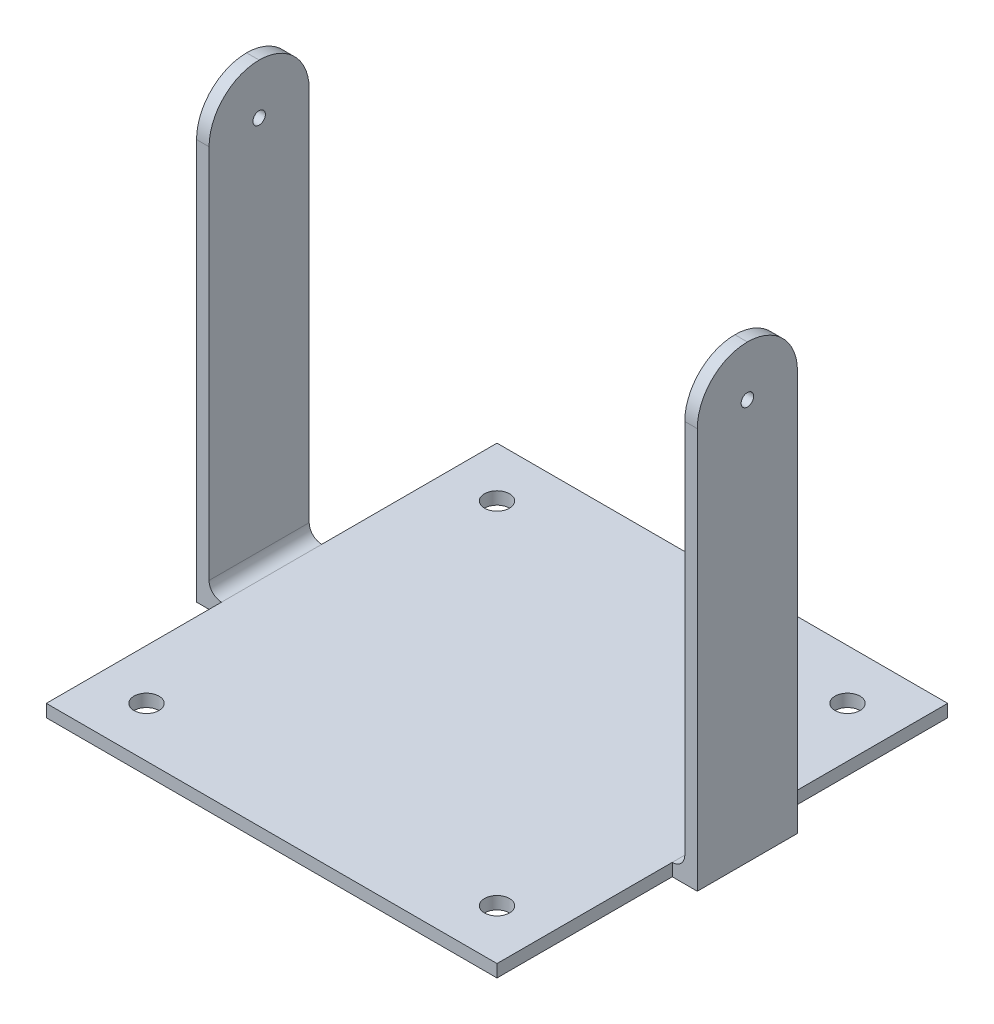
SolidWorks part; units mm, degrees
material "6061 Alloy"
ref_plane "Front Plane" through (0, 0, 0) normal (0, 0, 1) x (1, 0, 0)
ref_plane "Top Plane" through (0, 0, 0) normal (0, 1, 0) x (1, 0, 0)
ref_plane "Right Plane" through (0, 0, 0) normal (1, 0, 0) x (0, 0, -1)
sketch "Sketch1" plane through (0, 0, 0) normal (0, 1, 0) x (1, 0, 0)
  line L1 (0, 0) -> (228.6, 0)
  line L2 (0, 0) -> (0, 457.2)
  line L3 (0, 457.2) -> (228.6, 457.2)
  line L4 (228.6, 0) -> (228.6, 457.2)
  dimension "D1" = 228.6
  dimension "D2" = 457.2
extrude "Boss-Extrude1" add sketch "Sketch1" along normal blind 12.7
sketch "Sketch2" plane through (0, 12.7, 0) normal (0, 1, 0) x (1, 0, 0)
  line L0 (114.3, 457.2) -> (114.3, 0) construction
  line L1 (228.6, 457.2) -> (0, 457.2) construction
  line L2 (0, 0) -> (228.6, 0) construction
  line L3 (0, 228.6) -> (228.6, 228.6) construction
  line L4 (0, 457.2) -> (0, 0) construction
  line L5 (228.6, 0) -> (228.6, 457.2) construction
  line L7 (228.6, 279.4) -> (241.3, 279.4)
  line L8 (228.6, 279.4) -> (228.6, 177.8)
  line L9 (228.6, 177.8) -> (241.3, 177.8)
  line L10 (241.3, 279.4) -> (241.3, 177.8)
  dimension "D1" = 12.7
  dimension "D2" = 101.6
  dimension "D3" = 50.8
extrude "Boss-Extrude2" add sketch "Sketch2" against normal blind 12.7
sketch "Sketch3" plane through (241.3, 0, 0) normal (1, 0, 0) x (0, 0, -1)
  line L1 (177.8, 0) -> (279.4, 0)
  line L2 (177.8, 0) -> (177.8, 457.2)
  line L3 (177.8, 457.2) -> (279.4, 457.2)
  line L4 (279.4, 0) -> (279.4, 457.2)
  dimension "D1" = 101.6
  dimension "D2" = 457.2
extrude "Boss-Extrude3" add sketch "Sketch3" along normal blind 12.7
fillet "Fillet1" radius 12.7 1 edges
mirror "Mirror1" about plane through (0, 12.7, 0) normal (1, 0, 0) of "Boss-Extrude1", "Boss-Extrude2", "Boss-Extrude3", "Fillet1"
sketch "Sketch4" plane through (-254, 0, 0) normal (-1, 0, 0) x (0, 0, 1)
  line L0 (-279.4, 457.2) -> (-177.8, 457.2) construction
  line L1 (-279.4, 0) -> (-279.4, 457.2) construction
  circle A0 centre (-228.6, 406.4) radius 6.35
  dimension "D1" = 12.7
  dimension "D2" = 50.8
  dimension "D3" = 50.8
extrude "Cut-Extrude1" cut sketch "Sketch4" against normal through all
fillet "Fillet2" radius 50.8 1 edges at (-247.65, 457.2, -177.8)
fillet "Fillet3" radius 50.8 1 edges at (-247.65, 457.2, -279.4)
fillet "Fillet4" radius 50.8 1 edges at (247.65, 457.2, -177.8)
fillet "Fillet5" radius 50.8 1 edges at (247.65, 457.2, -279.4)
sketch "Sketch5" plane through (0, 12.7, 0) normal (0, 1, 0) x (1, 0, 0)
  line L0 (228.6, 457.2) -> (-228.6, 457.2) construction
  line L1 (-228.6, 279.4) -> (-228.6, 457.2) construction
  circle A0 centre (-177.8, 406.4) radius 12.7
  dimension "D1" = 25.4
  dimension "D2" = 50.8
  dimension "D3" = 50.8
extrude "Cut-Extrude2" cut sketch "Sketch5" against normal through all
sketch "Sketch6" plane through (0, 12.7, 0) normal (0, 1, 0) x (1, 0, 0)
  line L0 (228.6, 457.2) -> (-228.6, 457.2) construction
  line L1 (228.6, 279.4) -> (228.6, 457.2) construction
  line L2 (228.6, 0) -> (228.6, 177.8) construction
  line L3 (-228.6, 0) -> (228.6, 0) construction
  line L4 (-228.6, 0) -> (-228.6, 177.8) construction
  circle A0 centre (177.8, 406.4) radius 12.7
  circle A1 centre (-177.8, 50.8) radius 12.7
  circle A2 centre (177.8, 50.8) radius 12.7
  dimension "D1" = 25.4
  dimension "D2" = 25.4
  dimension "D3" = 25.4
  dimension "D4" = 50.8
  dimension "D5" = 50.8
  dimension "D6" = 50.8
  dimension "D7" = 50.8
  dimension "D8" = 50.8
  dimension "D9" = 50.8
extrude "Cut-Extrude3" cut sketch "Sketch6" against normal through all
